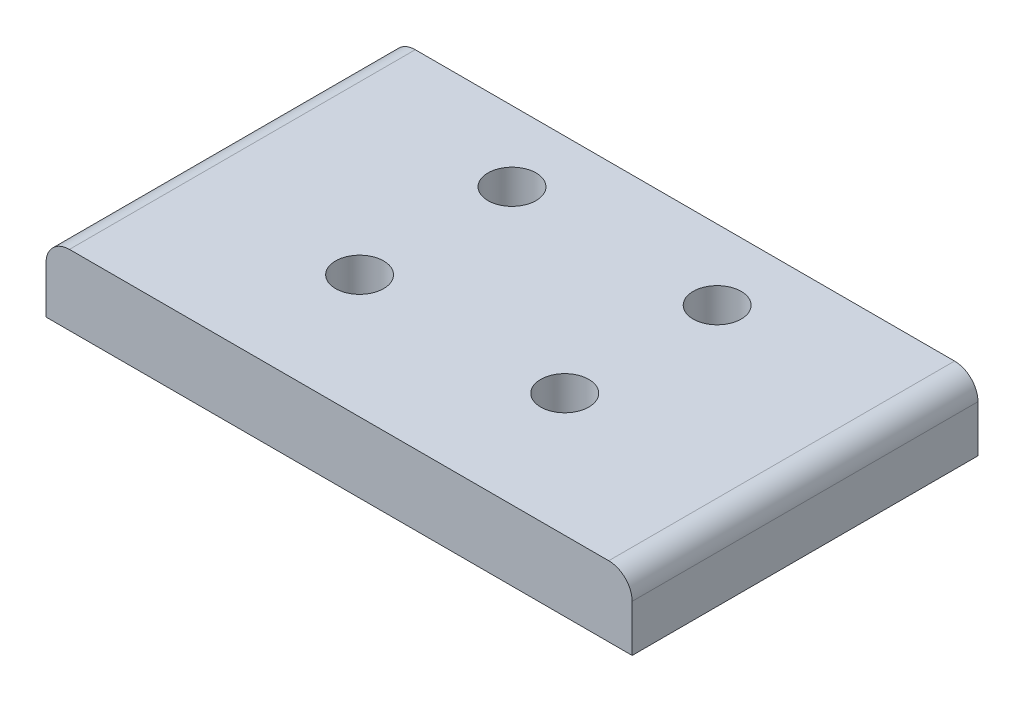
SolidWorks part; units mm, degrees
ref_plane "Front Plane" through (0, 0, 0) normal (0, 0, 1) x (1, 0, 0)
ref_plane "Top Plane" through (0, 0, 0) normal (0, 1, 0) x (1, 0, 0)
ref_plane "Right Plane" through (0, 0, 0) normal (1, 0, 0) x (0, 0, -1)
sketch "Sketch1" plane through (0, 0, 0) normal (0, 1, 0) x (1, 0, 0)
  line L0 (16.25, 0) -> (16.25, 29.5)
  line L1 (0, 0) -> (50, 0)
  line L2 (0, 0) -> (0, 29.5)
  line L3 (0, 29.5) -> (50, 29.5)
  line L4 (50, 0) -> (50, 29.5)
  line L5 (16.25, 10.5) -> (50, 10.5)
  line L6 (33.75, 0) -> (33.75, 29.5)
  line L7 (16.25, 23.5) -> (50, 23.5)
  dimension "D1" = 50
  dimension "D2" = 29.5
  dimension "D3" = 13
  dimension "D4" = 10.5
  dimension "D5" = 17.5
  dimension "D6" = 16.25
extrude "Boss-Extrude1" add sketch "Sketch1" along normal blind 6 contours L3 L2 L1 L0 | L0 L7 L6 L3 | L7 L0 L5 L6 | L7 L6 L5 L4 | L1 L6 L5 L0 | L6 L1 L4 L5 | L6 L7 L4 L3 region at (8.125, 0, -14.75) region at (25, 0, -5.25) region at (25, 0, -17) region at (41.875, 0, -5.25) region at (25, 0, -26.5) region at (41.875, 0, -17) region at (41.875, 0, -26.5)
fillet "Fillet1" radius 2 1 edges at (0, 6, -14.75)
fillet "Fillet2" radius 2 1 edges at (50, 6, -14.75)
sketch "Sketch4" plane through (0, 0, 0) normal (0, -1, 0) x (1, 0, 0)
  line L0 (33.75, 0) -> (33.75, -29.5) construction
  line L1 (16.25, -23.5) -> (33.75, -23.5)
  line L2 (16.25, -23.5) -> (16.25, -10.5)
  line L3 (16.25, -10.5) -> (33.75, -10.5)
  line L4 (33.75, -23.5) -> (33.75, -10.5)
  line L5 (16.25, -10.5) -> (50, -10.5) construction
  dimension "D1" = 0
  dimension "D2" = 0
hole_wizard "Ø4.0mm Dowel Hole2" positions "3DSketch3" profile "Sketch5" hole size "Ø4.0" standard "ANSI Metric" end condition through all
sketch3d "3DSketch3"
  point P0 (16.25, 0, -23.5)
  point P3 (33.75, 0, -23.5)
  point P6 (33.75, 0, -10.5)
  point P9 (16.25, 0, -10.5)
sketch "Sketch5" plane through (16.25, 0, -23.5) normal (1, 0, 0) x (0, 0, -1)
  line L0 (0, 0) -> (0, 6)
  line L1 (0, 6) -> (2.05, 6)
  line L2 (2.05, 6) -> (2.05, 0)
  line L5 (2.05, 0) -> (0, 0)
  line L11 (0, -6.35) -> (0, 107.95) construction
  dimension "Thru Hole Dia." = 4.1
  dimension "Thru Hole Depth" = 6
